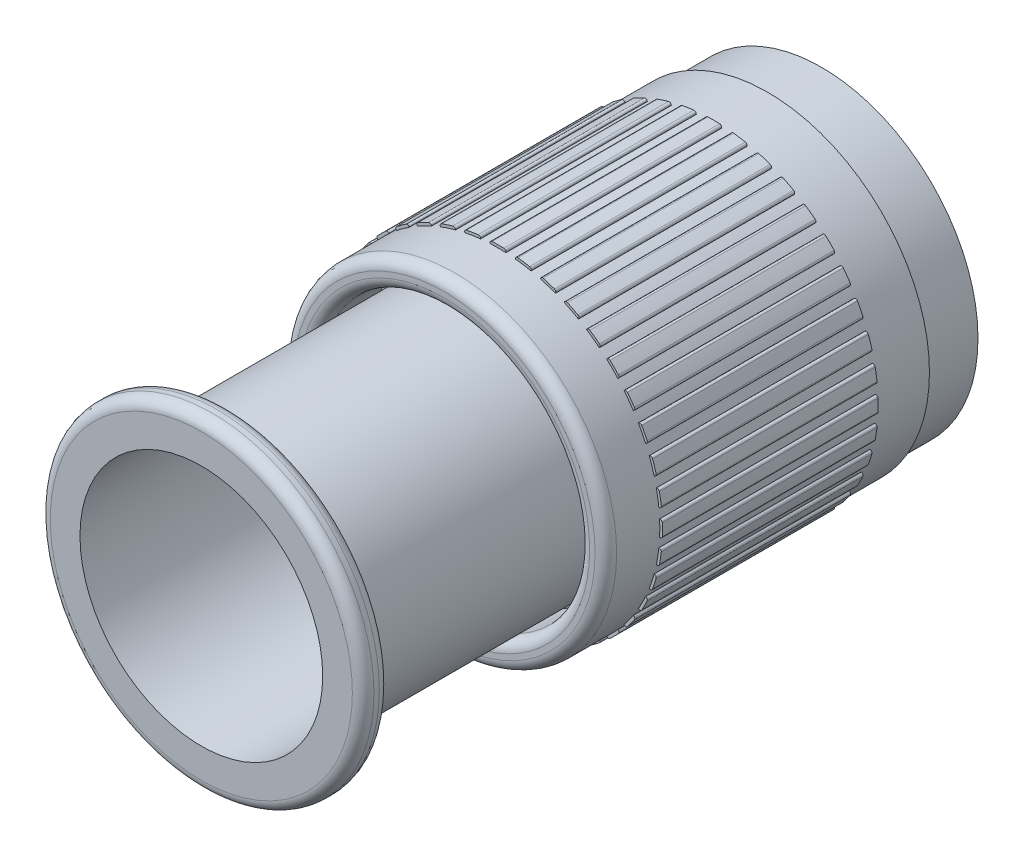
SolidWorks part; units mm, degrees
ref_plane "Front Plane" through (0, 0, 0) normal (0, 0, 1) x (1, 0, 0)
ref_plane "Top Plane" through (0, 0, 0) normal (0, 1, 0) x (1, 0, 0)
ref_plane "Right Plane" through (0, 0, 0) normal (1, 0, 0) x (0, 0, -1)
sketch "Sketch1" plane through (0, 0, 0) normal (0, 0, 1) x (1, 0, 0)
  circle A0 centre (0, 0) radius 29
  dimension "D1" = 58
extrude "Boss-Extrude1" add sketch "Sketch1" along normal blind 10
sketch "Sketch2" plane through (0, 0, 10) normal (0, 0, 1) x (1, 0, 0)
  circle A0 centre (0, 0) radius 30
  dimension "D1" = 60
extrude "Boss-Extrude2" add sketch "Sketch2" along normal blind 50
sketch "Sketch3" plane through (0, 0, 60) normal (0, 0, 1) x (1, 0, 0)
  line L0 (0, 0) -> (1.4754, 29.9637) construction
  line L1 (1.4754, 29.9637) -> (1.5246, 30.9625) construction
  line L2 (0, 0) -> (-1.4754, 29.9637) construction
  line L3 (-1.4754, 29.9637) -> (-1.7288, 35.1093) construction
  line L4 (-1.4802, 30.0609) -> (-1.4754, 29.9637)
  line L5 (1.4802, 30.0609) -> (1.4754, 29.9637)
  arc A0 (-1.4754, 29.9637) -> (1.4754, 29.9637) centre (0, 0) cw
  circle A1 centre (0, 0) radius 30 construction
  arc A3 (1.095, 30.4803) -> (-1.095, 30.4803) centre (0, 0) ccw
  arc A4 (1.095, 30.4803) -> (1.4802, 30.0609) centre (1.0807, 30.0806) cw
  arc A5 (-1.095, 30.4803) -> (-1.4802, 30.0609) centre (-1.0807, 30.0806) ccw
  point P13 (1.5, 30.4631)
  point P16 (-1.5, 30.4631)
  dimension "D1" = 1.5
  dimension "D3" = 30.5
  dimension "D4" = 0.4
  dimension "D2" = 1.5
extrude "Boss-Extrude3" add sketch "Sketch3" against normal blind 40
pattern_circular "CirPattern1" count 40 over 360 about axis through (0, 0, 10) along (0, 0, -1) of "Boss-Extrude3"
sketch "Sketch4" plane through (0, 0, 60) normal (0, 0, 1) x (1, 0, 0)
  circle A0 centre (0, 0) radius 30
  dimension "D1" = 60
extrude "Boss-Extrude4" add sketch "Sketch4" along normal blind 10
sketch "Sketch5" plane through (0, 0, 70) normal (0, 0, 1) x (1, 0, 0)
  circle A0 centre (0, 0) radius 25
  dimension "D1" = 50
extrude "Cut-Extrude1" cut sketch "Sketch5" against normal blind 10
fillet "Fillet1" radius 2 2 edges at (30, 0, 70) (25, 0, 70)
sketch "Sketch6" plane through (0, 0, 60) normal (0, 0, 1) x (1, 0, 0)
  circle A0 centre (0, 0) radius 24
  dimension "D1" = 48
extrude "Boss-Extrude5" add sketch "Sketch6" along normal blind 50
sketch "Sketch7" plane through (0, 0, 110) normal (0, 0, 1) x (1, 0, 0)
  circle A0 centre (0, 0) radius 30
  dimension "D1" = 60
extrude "Boss-Extrude6" add sketch "Sketch7" along normal blind 5
fillet "Fillet2" radius 2 2 edges at (30, 0, 110) (30, 0, 115)
sketch "Sketch9" plane through (0, 0, 115) normal (0, 0, 1) x (1, 0, 0)
  circle A0 centre (0, 0) radius 22.5
  dimension "D1" = 45
extrude "Cut-Extrude3" cut sketch "Sketch9" against normal through all
scale "Scale1" scale about centroid uniform scaling yes scale factor 0.75
